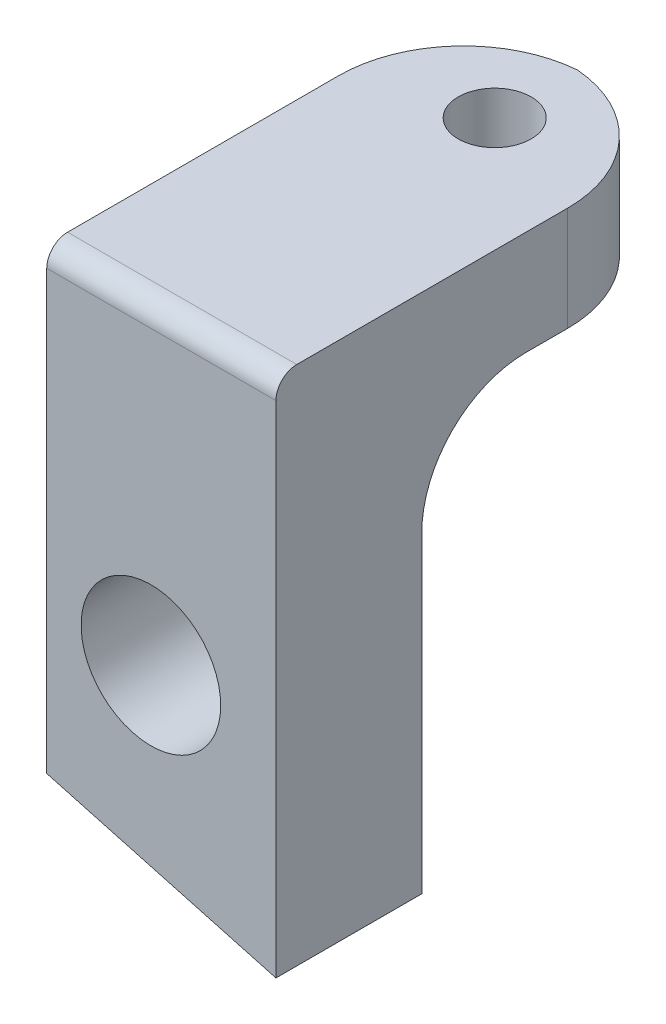
SolidWorks part; units mm, degrees
ref_plane "Спереди" through (0, 0, 0) normal (0, 0, 1) x (1, 0, 0)
ref_plane "Сверху" through (0, 0, 0) normal (0, 1, 0) x (1, 0, 0)
ref_plane "Справа" through (0, 0, 0) normal (1, 0, 0) x (0, 0, -1)
sketch "Эскиз1" plane through (0, 0, 0) normal (0, 0, 1) x (1, 0, 0)
  line L1 (-5, 10) -> (6, 10)
  line L2 (-5, 10) -> (-5, -7)
  line L3 (-5, -7) -> (6, -10)
  line L4 (6, 10) -> (6, -10)
  circle A0 centre (0, 0) radius 3.35
  dimension "D1" = 6.7
  dimension "D2" = 11
  dimension "D3" = 6
  dimension "D4" = 10
  dimension "D5" = 3
  dimension "D6" = 20
extrude "Бобышка-Вытянуть1" add sketch "Эскиз1" along normal blind 7
sketch "Эскиз2" plane through (0, 10, 0) normal (0, 1, 0) x (1, 0, 0)
  line L1 (-5, -7) -> (6, -7)
  line L2 (-5, -7) -> (-5, 13)
  line L3 (-5, 13) -> (6, 13)
  line L4 (6, -7) -> (6, 13)
  dimension "D1" = 11
  dimension "D2" = 20
extrude "Бобышка-Вытянуть2" add sketch "Эскиз2" along normal blind 5
fillet "Скругление1" radius 5 1 edges at (0.5, 10, 0)
fillet "Скругление2" radius 1 1 edges at (3.35, 0, 0)
fillet "Скругление4" radius 1 1 edges at (0.5, 15, 7)
sketch "Эскиз3" plane through (0, 10, 0) normal (0, -1, 0) x (1, 0, 0)
  line L0 (0.5, -13) -> (0.5, -5) construction
  line L7 (6, -13) -> (-5, -13) construction
  line L8 (6, -5) -> (-5, -5) construction
  circle A0 centre (0.5, -9) radius 1.75
  dimension "D1" = 3.5
fillet "Скругление11" radius 6 2 edges at (6, 12.5, -13) (-5, 12.5, -13)
extrude "Вырез-Вытянуть2" cut sketch "Эскиз3" against normal blind 10
